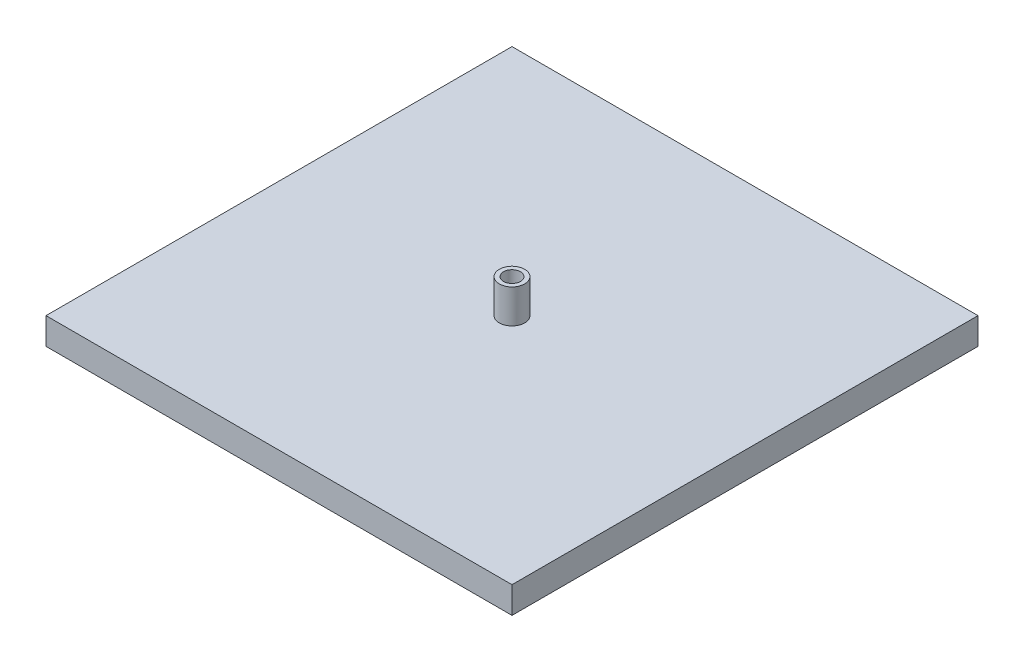
SolidWorks part; units mm, degrees
ref_plane "Front" through (0, 0, 0) normal (0, 0, 1) x (1, 0, 0)
ref_plane "Top" through (0, 0, 0) normal (0, 1, 0) x (1, 0, 0)
ref_plane "Right" through (0, 0, 0) normal (1, 0, 0) x (0, 0, -1)
sketch "Sketch2" plane through (0, 0, 0) normal (0, 1, 0) x (1, 0, 0)
  line L1 (0, 0) -> (350, 0)
  line L2 (0, 0) -> (0, 350)
  line L3 (0, 350) -> (350, 350)
  line L4 (350, 0) -> (350, 350)
  dimension "D1" = 350
  dimension "D2" = 350
extrude "Boss-Extrude1" add sketch "Sketch2" along normal blind 20
sketch "Sketch3" plane through (0, 20, 0) normal (0, 1, 0) x (1, 0, 0)
  line L4 (350, 350) -> (0, 350) construction
  line L5 (0, 0) -> (350, 0) construction
  line L6 (175, 350) -> (175, 0) construction
  line L7 (350, 175) -> (0, 175) construction
  line L8 (350, 0) -> (350, 350) construction
  line L9 (0, 350) -> (0, 0) construction
  circle A0 centre (175, 175) radius 6.35
  circle A1 centre (175, 175) radius 9.525
  point P15 (0, 0)
  dimension "D1" = 12.7
  dimension "D2" = 19.05
extrude "Cut-Extrude1" cut sketch "Sketch3" against normal through all contours A0
extrude "Boss-Extrude2" add sketch "Sketch3<3>" along normal blind 25.4
sketch "Sketch3<3>" plane through (0, 20, 0) normal (0, 1, 0) x (1, 0, 0) same geometry as "Sketch3"
